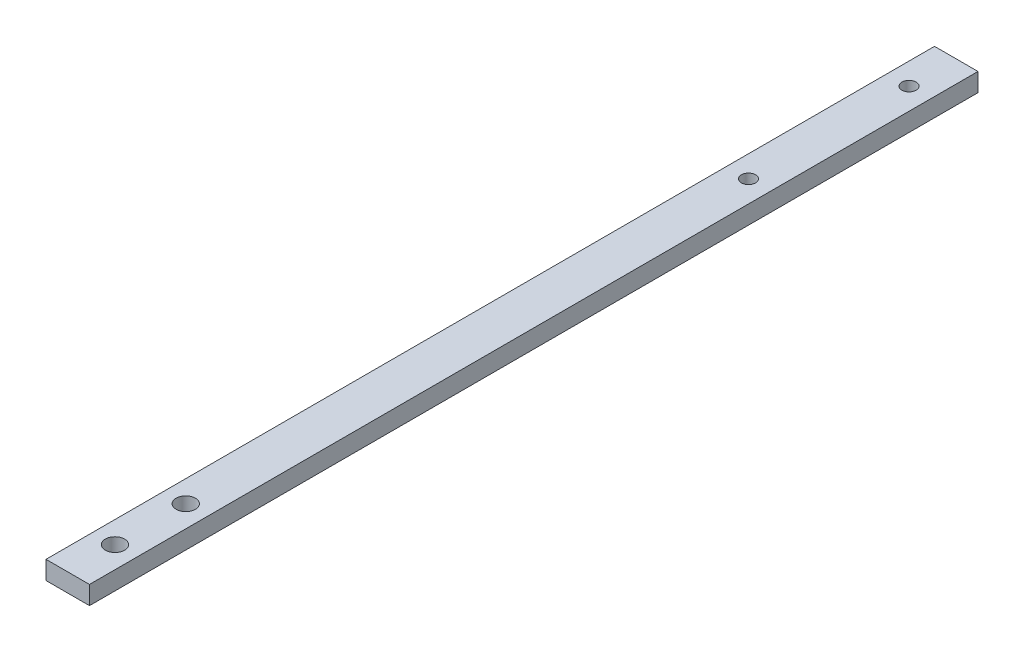
SolidWorks part; units mm, degrees
ref_plane "Front Plane" through (0, 0, 0) normal (0, 0, 1) x (1, 0, 0)
ref_plane "Top Plane" through (0, 0, 0) normal (0, 1, 0) x (1, 0, 0)
ref_plane "Right Plane" through (0, 0, 0) normal (1, 0, 0) x (0, 0, -1)
sketch "Sketch1" plane through (0, 0, 0) normal (0, 0, 1) x (1, 0, 0)
  circle A0 centre (0, 0) radius 2.5
  dimension "D1" = 5
extrude "Boss-Extrude1" add sketch "Sketch1" along normal blind 56
sketch "Sketch2" plane through (0, 0, 56) normal (0, 0, 1) x (1, 0, 0)
  line L1 (2.3024, -0.9741) -> (-2.3024, -0.9741)
  line L2 (2.3024, -0.9741) -> (2.3024, 0.9741)
  line L3 (2.3024, 0.9741) -> (-2.3024, 0.9741)
  line L4 (-2.3024, -0.9741) -> (-2.3024, 0.9741)
  line L5 (2.3024, -0.9741) -> (-2.3024, 0.9741) construction
  line L6 (2.3024, 0.9741) -> (-2.3024, -0.9741) construction
  circle A0 centre (0, 0) radius 2.5 construction
  point P0 (0, 0)
extrude "Boss-Extrude2" add sketch "Sketch2" along normal blind 38.1
sketch "Sketch3" plane through (0, 0.9741, 0) normal (0, 1, 0) x (1, 0, 0)
  line L0 (2.3024, -94.1) -> (-2.3024, -94.1) construction
  circle A0 centre (0, -81.6) radius 1.0227
  circle A1 centre (0, -89.1) radius 1.0227
  point P6 (0, -94.1)
  dimension "D1" = 5
  dimension "D2" = 12.5
extrude "Cut-Extrude1" cut sketch "Sketch3" against normal through all
sketch "Sketch4" plane through (0, 0, 0) normal (0, 1, 0) x (1, 0, 0)
  line L0 (0, 0) -> (0, -14.2164) construction
  line L1 (2.5, 0) -> (-2.5, 0) construction
  circle A0 centre (0, -5) radius 0.75
  circle A1 centre (0, -22) radius 0.75
  dimension "D1" = 1.5
  dimension "D2" = 1.5
  dimension "D3" = 17
  dimension "D4" = 5
extrude "Cut-Extrude2" cut sketch "Sketch4" against normal through all and the other way through all
sketch "Sketch5" plane through (0, 0, 94.1) normal (0, 0, 1) x (1, 0, 0)
  line L1 (-2.3024, 0.9741) -> (2.3024, 0.9741)
  line L2 (-2.3024, 0.9741) -> (-2.3024, -0.9741)
  line L3 (-2.3024, -0.9741) -> (2.3024, -0.9741)
  line L4 (2.3024, 0.9741) -> (2.3024, -0.9741)
extrude "Cut-Extrude3" cut sketch "Sketch5" against normal through all flip side to cut
